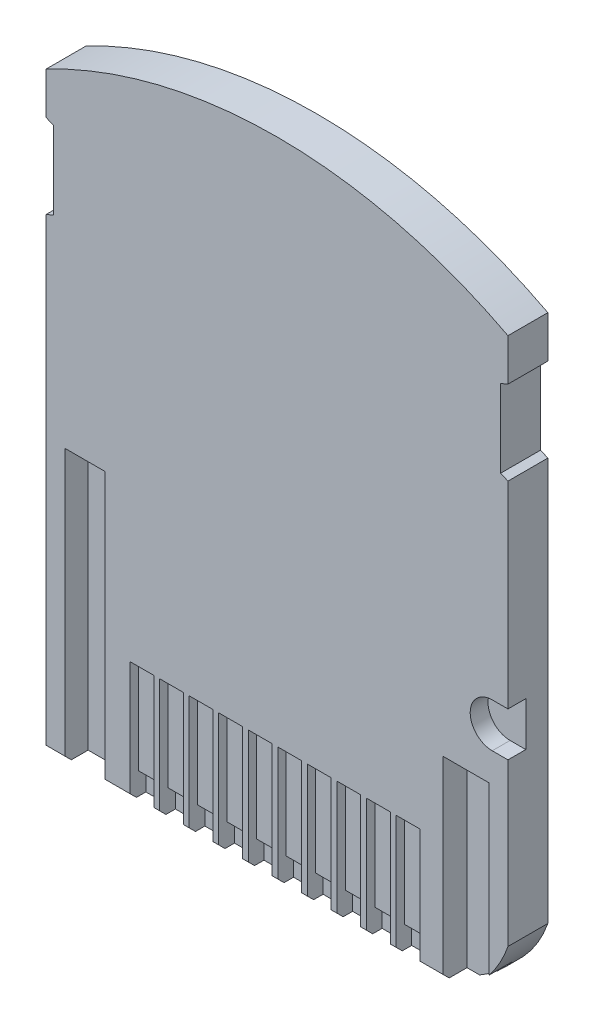
SolidWorks part; units mm, degrees
ref_plane "Front Plane" through (0, 0, 0) normal (0, 0, 1) x (1, 0, 0)
ref_plane "Top Plane" through (0, 0, 0) normal (0, 1, 0) x (1, 0, 0)
ref_plane "Right Plane" through (0, 0, 0) normal (1, 0, 0) x (0, 0, -1)
sketch "Sketch1" plane through (0, 0, 0) normal (0, 1, 0) x (1, 0, 0)
  line L1 (-11, -0.95) -> (11, -0.95)
  line L2 (-11, -0.95) -> (-11, 0.95)
  line L3 (-11, 0.95) -> (11, 0.95)
  line L4 (11, -0.95) -> (11, 0.95)
  line L5 (-11, -0.95) -> (11, 0.95) construction
  line L6 (-11, 0.95) -> (11, -0.95) construction
  point P0 (0, 0)
  dimension "D1" = 1.9
  dimension "D2" = 22
extrude "Boss-Extrude1" add sketch "Sketch1" along normal blind 31.1
sketch "Sketch2" plane through (0, 0, 0.95) normal (0, 0, 1) x (1, 0, 0)
  line L0 (-11, 0) -> (8.5, 0)
  line L1 (0, 0) -> (0, 1.05)
  line L2 (5.663, 1.05) -> (6.8, 1.05)
  line L3 (10.25, 12.8) -> (11, 12.8)
  line L4 (11, 12.8) -> (11, 22.2)
  line L5 (-7, 5.75) -> (-7, 0)
  line L6 (2.849, 1.05) -> (3.986, 1.05)
  line L7 (10.25, 10.7) -> (11, 10.7)
  line L8 (1.442, 1.05) -> (2.579, 1.05)
  line L9 (0.035, 1.05) -> (1.172, 1.05)
  line L10 (10.1, 1.3679) -> (10.1, 9.3)
  line L11 (10.1, 9.3) -> (7.9, 9.3)
  line L12 (-10.1, 13) -> (-10.1, 0)
  line L13 (-10.1, 13) -> (-8.2, 13)
  line L14 (7.9, 9.3) -> (7.9, 0)
  line L15 (-8.2, 13) -> (-8.2, 0)
  line L16 (-1.372, 1.05) -> (-0.235, 1.05)
  line L17 (7.9, 0) -> (8.5, 0)
  line L18 (0, 0) -> (0, 30.9) construction
  line L19 (-11, 0) -> (-11, 22.2)
  line L20 (11, 3) -> (11, 10.7)
  line L21 (10.1, 9.3) -> (10.1, 10.7)
  line L22 (11, 26.2) -> (11, 28.2)
  line L23 (-7, 5.75) -> (6.8, 5.75)
  line L24 (6.8, 5.75) -> (6.8, 0)
  line L25 (-7, 1.05) -> (-5.863, 1.05)
  line L26 (-2.779, 1.05) -> (-1.642, 1.05)
  line L27 (-4.186, 1.05) -> (-3.049, 1.05)
  line L28 (-5.593, 1.05) -> (-4.456, 1.05)
  line L29 (4.256, 1.05) -> (5.393, 1.05)
  line L30 (-11, 26.2) -> (-11, 28.2)
  line L44 (-5.863, 5.75) -> (-5.863, 0)
  line L46 (-5.593, 5.75) -> (-5.593, 0)
  line L47 (-4.456, 5.75) -> (-4.456, 0)
  line L48 (-4.186, 5.75) -> (-4.186, 0)
  line L49 (-3.049, 5.75) -> (-3.049, 0)
  line L50 (-2.779, 5.75) -> (-2.779, 0)
  line L51 (-1.642, 5.75) -> (-1.642, 0)
  line L52 (-1.372, 5.75) -> (-1.372, 0)
  line L53 (-0.235, 5.75) -> (-0.235, 0)
  line L54 (0.035, 5.75) -> (0.035, 0)
  line L55 (1.172, 5.75) -> (1.172, 0)
  line L56 (1.442, 5.75) -> (1.442, 0)
  line L57 (2.579, 5.75) -> (2.579, 0)
  line L58 (2.849, 5.75) -> (2.849, 0)
  line L59 (3.986, 5.75) -> (3.986, 0)
  line L60 (4.256, 5.75) -> (4.256, 0)
  line L61 (5.393, 5.75) -> (5.393, 0)
  line L62 (5.663, 5.75) -> (5.663, 0)
  line L63 (-10.65, 23.2527) -> (10.65, 23.2527) construction
  line L64 (11, 28.2) -> (11, 26.2)
  line L66 (-10.65, 22.35) -> (-11, 22.2)
  line L67 (10.65, 26.05) -> (10.65, 22.35)
  line L68 (-10.65, 26.05) -> (-11, 26.2)
  line L70 (-10.65, 26.05) -> (-10.65, 22.35)
  line L72 (10.65, 22.35) -> (11, 22.2)
  line L73 (10.65, 26.05) -> (11, 26.2)
  arc A0 (8.5, 0) -> (11, 3) centre (5.7589, 4.8259) ccw
  arc A1 (-11, 28.2) -> (11, 28.2) centre (0, 7.1426) cw
  arc A2 (10.25, 12.8) -> (10.25, 10.7) centre (10.25, 11.75) ccw
  line M5 (-11, 0) -> (11, 0)
  line M6 (11, 0) -> (11, 31.1)
  line M7 (11, 31.1) -> (-11, 31.1)
  line M8 (-11, 31.1) -> (-11, 0)
  dimension "D12" = 5.55
  dimension "D16" = 23.7574
  dimension "D19" = 1.05
  dimension "D1" = 1.05
  dimension "D4" = 1.137
  dimension "D5" = 0.9
  dimension "D6" = 2.2
  dimension "D7" = 13
  dimension "D8" = 1.9
  dimension "D9" = 0.9
  dimension "D10" = 22
  dimension "D11" = 0.6
  dimension "D13" = 30.9
  dimension "D14" = 28.2
  dimension "D18" = 1.4
  dimension "D20" = 0.75
  dimension "D21" = 4.7
  dimension "D22" = 13.8
  dimension "D24" = 0.27
  dimension "D26" = 21.3
  dimension "D27" = 2
  dimension "D28" = 4
  dimension "D29" = 0.15
  dimension "D30" = 0.35
extrude "Cut-Extrude2" cut sketch "Sketch2" against normal up to next contours A1 M8 M6 M7 region at (-10.7781, 29.65, 0.95)
extrude "Cut-Extrude3" cut sketch "Sketch2<4>" against normal up to next contours L70 L68 L66 M8 | L73 L67 L72 M6 | A0 M5 M6 region at (-10.8273, 24.2, 0.95) region at (10.8273, 24.2, 0.95) region at (10.268, 0.8652, 0.95)
sketch "Sketch2<4>" plane through (0, 0, 0.95) normal (0, 0, 1) x (1, 0, 0) same geometry as "Sketch2"
extrude "Cut-Extrude4" cut sketch "Sketch2<5>" against normal blind 0.85 contours L3 A2 L7 M6 region at (10.1952, 11.75, 0.95)
sketch "Sketch2<5>" plane through (0, 0, 0.95) normal (0, 0, 1) x (1, 0, 0) same geometry as "Sketch2"
chamfer "Chamfer1" distance 0.3 angle 45 1 edges at (-1.25, 0, 0.95)
extrude "Cut-Extrude6" cut sketch "Sketch2<8>" against normal blind 1.1 contours L15 L13 L12 L0 region at (-9.15, 6.5, 0.95)
sketch "Sketch2<8>" plane through (0, 0, 0.95) normal (0, 0, 1) x (1, 0, 0) same geometry as "Sketch2"
extrude "Cut-Extrude7" cut sketch "Sketch2<9>" against normal blind 1.15 contours A0 L10 L11 L14 M5 region at (8.9706, 4.8563, 0.95)
sketch "Sketch2<9>" plane through (0, 0, 0.95) normal (0, 0, 1) x (1, 0, 0) same geometry as "Sketch2"
extrude "Cut-Extrude8" cut sketch "Sketch2<10>" against normal blind 0.75 contours L44 L25 L5 L0 | L47 L28 L46 L0 | L49 L27 L48 L0 | L51 L26 L50 L0 | L53 L16 L52 L0 | L55 L9 L54 M5 | L57 L8 L56 M5 | L59 L6 L58 M5 | L61 L29 L60 M5 | L2 L62 L24 M5 region at (-6.4315, 0.525, 0.95) region at (-5.0245, 0.525, 0.95) region at (-3.6175, 0.525, 0.95) region at (-2.2105, 0.525, 0.95) region at (-0.8035, 0.525, 0.95) region at (0.6035, 0.525, 0.95) region at (2.0105, 0.525, 0.95) region at (3.4175, 0.525, 0.95) region at (6.2315, 0.525, 0.95) region at (4.8245, 0.525, 0.95)
sketch "Sketch2<10>" plane through (0, 0, 0.95) normal (0, 0, 1) x (1, 0, 0) same geometry as "Sketch2"
extrude "Cut-Extrude9" cut sketch "Sketch2<11>" against normal blind 0.4 contours L44 L23 L5 L25 | L47 L23 L46 L28 | L49 L23 L48 L27 | L51 L23 L50 L26 | L53 L23 L52 L16 | L55 L23 L54 L9 | L57 L23 L56 L8 | L59 L23 L58 L6 | L61 L23 L60 L29 | L23 L62 L2 L24 region at (-6.4315, 3.4, 0.95) region at (-5.0245, 3.4, 0.95) region at (-3.6175, 3.4, 0.95) region at (-2.2105, 3.4, 0.95) region at (-0.8035, 3.4, 0.95) region at (0.6035, 3.4, 0.95) region at (2.0105, 3.4, 0.95) region at (3.4175, 3.4, 0.95) region at (6.2315, 3.4, 0.95) region at (4.8245, 3.4, 0.95)
sketch "Sketch2<11>" plane through (0, 0, 0.95) normal (0, 0, 1) x (1, 0, 0) same geometry as "Sketch2"
sketch "Sketch5" plane through (0, 0, -0.95) normal (0, 0, -1) x (-1, 0, 0)
  line L1 (-9.4, 4.6) -> (-9.4, 27.2073)
  line L3 (9.4, 4.6) -> (9.4, 27.2073)
  line L5 (-9.4, 4.6) -> (9.4, 4.6)
  arc A1 (9.4, 27.2073) -> (-9.4, 27.2073) centre (0, 7.1426) ccw
extrude "Cut-Extrude10" cut sketch "Sketch5" against normal blind 0.2
sketch "Sketch6" plane through (0, 0, -0.95) normal (0, 0, -1) x (-1, 0, 0)
  line L2 (-3.15, 3.4807) -> (3.15, 3.4807)
  line L4 (-3.15, 3.4807) -> (0, 1.5807)
  line L5 (3.15, 3.4807) -> (0, 1.5807)
  dimension "D2" = 6.3
extrude "Cut-Extrude12" cut sketch "Sketch6" against normal blind 0.1
